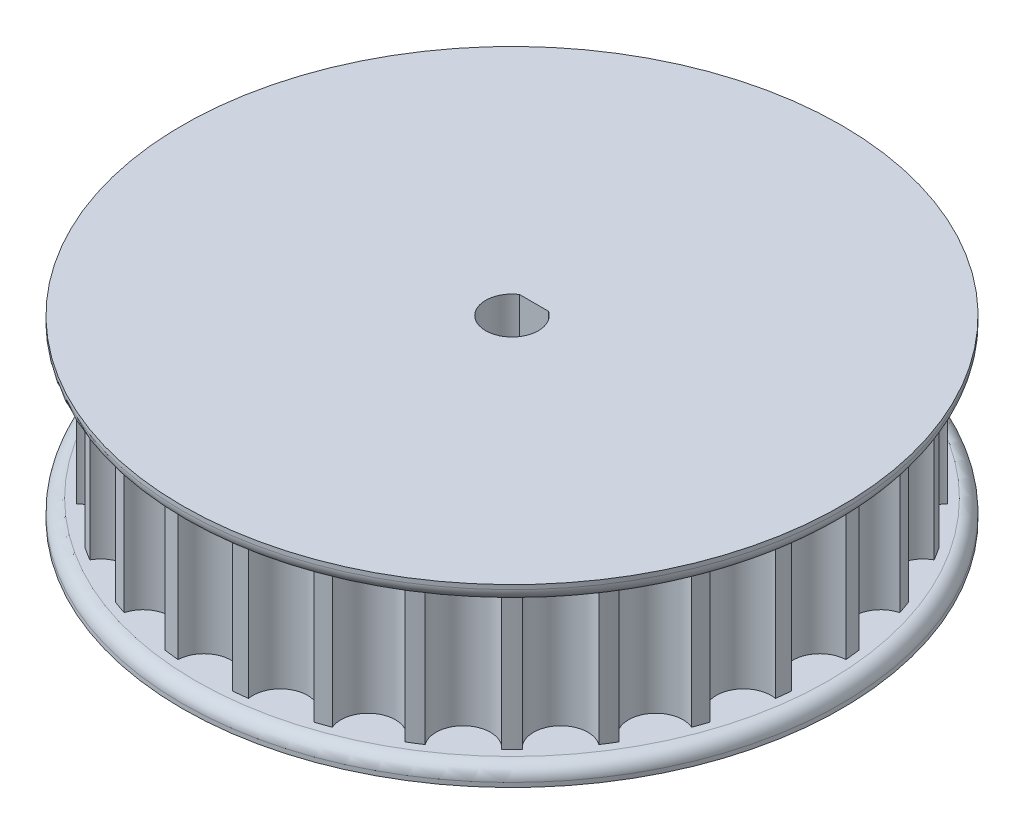
SolidWorks part; units mm, degrees
ref_plane "Front Plane" through (0, 0, 0) normal (0, 0, 1) x (1, 0, 0)
ref_plane "Top Plane" through (0, 0, 0) normal (0, 1, 0) x (1, 0, 0)
ref_plane "Right Plane" through (0, 0, 0) normal (1, 0, 0) x (0, 0, -1)
sketch "Sketch1" plane through (0, 0, 0) normal (0, 1, 0) x (1, 0, 0)
  line L0 (-1.6583, 2.5) -> (1.6583, 2.5)
  arc A0 (-3.097, 34.9029) -> (3.097, 34.9029) centre (0, 35.04) ccw
  circle A1 centre (0, 0) radius 35.04
  arc A2 (4.7473, 34.7169) -> (10.7859, 33.3386) centre (7.7971, 34.1615) ccw
  arc A3 (12.3535, 32.7901) -> (17.9341, 30.1027) centre (15.2033, 31.5699) ccw
  arc A4 (19.3403, 29.2191) -> (24.1829, 25.3572) centre (21.8471, 27.3954) ccw
  arc A5 (25.3572, 24.1829) -> (29.2191, 19.3403) centre (27.3954, 21.8471) ccw
  arc A6 (30.1027, 17.9341) -> (32.7901, 12.3535) centre (31.5699, 15.2033) ccw
  arc A7 (33.3386, 10.7859) -> (34.7169, 4.7473) centre (34.1615, 7.7971) ccw
  arc A8 (34.9029, 3.097) -> (34.9029, -3.097) centre (35.04, 0) ccw
  arc A9 (34.7169, -4.7473) -> (33.3386, -10.7859) centre (34.1615, -7.7971) ccw
  arc A10 (32.7901, -12.3535) -> (30.1027, -17.9341) centre (31.5699, -15.2033) ccw
  arc A11 (29.2191, -19.3403) -> (25.3572, -24.1829) centre (27.3954, -21.8471) ccw
  arc A12 (24.1829, -25.3572) -> (19.3403, -29.2191) centre (21.8471, -27.3954) ccw
  arc A13 (17.9341, -30.1027) -> (12.3535, -32.7901) centre (15.2033, -31.5699) ccw
  arc A14 (10.7859, -33.3386) -> (4.7473, -34.7169) centre (7.7971, -34.1615) ccw
  arc A15 (3.097, -34.9029) -> (-3.097, -34.9029) centre (0, -35.04) ccw
  arc A16 (-4.7473, -34.7169) -> (-10.7859, -33.3386) centre (-7.7971, -34.1615) ccw
  arc A17 (-12.3535, -32.7901) -> (-17.9341, -30.1027) centre (-15.2033, -31.5699) ccw
  arc A18 (-19.3403, -29.2191) -> (-24.1829, -25.3572) centre (-21.8471, -27.3954) ccw
  arc A19 (-25.3572, -24.1829) -> (-29.2191, -19.3403) centre (-27.3954, -21.8471) ccw
  arc A20 (-30.1027, -17.9341) -> (-32.7901, -12.3535) centre (-31.5699, -15.2033) ccw
  arc A21 (-33.3386, -10.7859) -> (-34.7169, -4.7473) centre (-34.1615, -7.7971) ccw
  arc A22 (-34.9029, -3.097) -> (-34.9029, 3.097) centre (-35.04, 0) ccw
  arc A23 (-34.7169, 4.7473) -> (-33.3386, 10.7859) centre (-34.1615, 7.7971) ccw
  arc A24 (-32.7901, 12.3535) -> (-30.1027, 17.9341) centre (-31.5699, 15.2033) ccw
  arc A25 (-29.2191, 19.3403) -> (-25.3572, 24.1829) centre (-27.3954, 21.8471) ccw
  arc A26 (-24.1829, 25.3572) -> (-19.3403, 29.2191) centre (-21.8471, 27.3954) ccw
  arc A27 (-17.9341, 30.1027) -> (-12.3535, 32.7901) centre (-15.2033, 31.5699) ccw
  arc A28 (-10.7859, 33.3386) -> (-4.7473, 34.7169) centre (-7.7971, 34.1615) ccw
  arc A29 (-1.6583, 2.5) -> (1.6583, 2.5) centre (0, 0) ccw
  point P8 (0, 31.94)
  point P90 (0, 0)
  point P92 (0, 2.5)
  dimension "D2" = 70.08
  dimension "D4" = 6
  dimension "D5" = 2.5
  dimension "D1" = 3.1
  dimension "D3" = 28
extrude "Boss-Extrude1" add sketch "Sketch1" along normal mid plane 16 contours A1 A26 A25 A24 A23 A22 A21 A20 A19 A18 A17 A16 A15 A14 A13 A12 A11 A10 A9 A8 A7 A6 A5 A4 A3 region at (0, 0, -30.9528)
sketch "Sketch2" plane through (0, 8, 0) normal (0, 1, 0) x (1, 0, 0)
  line L0 (-1.6583, 2.5) -> (1.6583, 2.5) construction
  line L1 (-1.6583, 2.5) -> (1.6583, 2.5)
  circle A1 centre (0, 0) radius 37.5
  arc A2 (-1.6583, 2.5) -> (1.6583, 2.5) centre (0, 0) ccw construction
  arc A3 (-1.6583, 2.5) -> (1.6583, 2.5) centre (0, 0) ccw
  dimension "D1" = 75
extrude "Boss-Extrude2" add sketch "Sketch2" along normal blind 2
fillet "Fillet1" radius 1.5 1 edges at (0, 8, 37.5)
mirror "Mirror1" about plane through (0, 0, 0) normal (0, 1, 0) of "Boss-Extrude2", "Fillet1"
sketch "Sketch3" plane through (0, 0, 0) normal (0, 0, 1) x (1, 0, 0)
  line L1 (0, -3.1754) -> (2.75, -1.5877)
  line L2 (2.75, -1.5877) -> (2.75, 1.5877)
  line L3 (2.75, 1.5877) -> (0, 3.1754)
  line L4 (0, 3.1754) -> (-2.75, 1.5877)
  line L5 (-2.75, 1.5877) -> (-2.75, -1.5877)
  line L6 (-2.75, -1.5877) -> (0, -3.1754)
  circle A0 centre (0, 0) radius 1.6
  circle A1 centre (0, 0) radius 2.75 construction
  point P3 (1.375, 2.3816)
  dimension "D1" = 3.2
  dimension "D2" = 5.5
extrude "Cut-Extrude1" cut sketch "Sketch3" against normal through all contours A0 region at (0, 0, 0)
extrude "Cut-Extrude2" cut sketch "Sketch3<3>" against normal blind 4.1 from offset 10 offset against normal yes
sketch "Sketch3<3>" plane through (0, 0, 0) normal (0, 0, 1) x (1, 0, 0) same geometry as "Sketch3"
sketch "Sketch4" plane through (0, -10, 0) normal (0, -1, 0) x (-1, 0, 0)
  line L0 (0, 0) -> (0, 10) construction
  line L1 (2.75, 10) -> (-2.75, 10)
  line L2 (2.75, 10) -> (2.75, 14.1)
  line L3 (2.75, 14.1) -> (-2.75, 14.1)
  line L4 (-2.75, 10) -> (-2.75, 14.1)
  line L5 (1.6, 10) -> (-1.6, 10) construction
  dimension "D1" = 4.1
  dimension "D2" = 5.5
extrude "Cut-Extrude3" cut sketch "Sketch4" against normal blind 10
sketch "Sketch5" plane through (0, 0, -14.1) normal (0, 0, 1) x (1, 0, 0)
  circle A0 centre (0, 0) radius 2.9
  dimension "D1" = 5.8
extrude "Cut-Extrude4" cut sketch "Sketch5" against normal through all from offset 5 offset against normal yes
